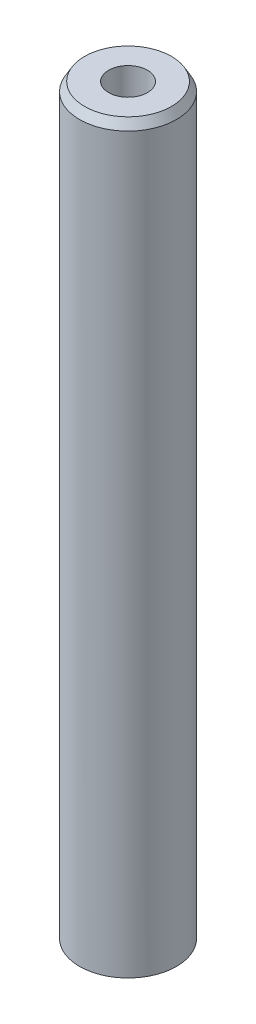
SolidWorks part; units mm, degrees
ref_plane "Front Plane" through (0, 0, 0) normal (0, 0, 1) x (1, 0, 0)
ref_plane "Top Plane" through (0, 0, 0) normal (0, 1, 0) x (1, 0, 0)
ref_plane "Right Plane" through (0, 0, 0) normal (1, 0, 0) x (0, 0, -1)
sketch "Sketch1" plane through (0, 0, 0) normal (0, 1, 0) x (1, 0, 0)
  circle A0 centre (0, 0) radius 5
  dimension "SHAFT_OD" = 10
extrude "Boss-Extrude1" add sketch "Sketch1" along normal blind 77.0648
sketch "Sketch2" plane through (0, 0, 0) normal (0, 1, 0) x (1, 0, 0)
  circle A0 centre (0, 0) radius 2.0033
  dimension "BORE_D" = 4.0065
extrude "Cut-Extrude1" cut sketch "Sketch2" along normal through all
chamfer "Chamfer1" distance 0.9056 angle 30 2 edges at (0, 77.0648, 5) (0, 0, 5) first distance on face at (0, 77.0648, 5) first distance on face at (0, 0, 2.0033)
